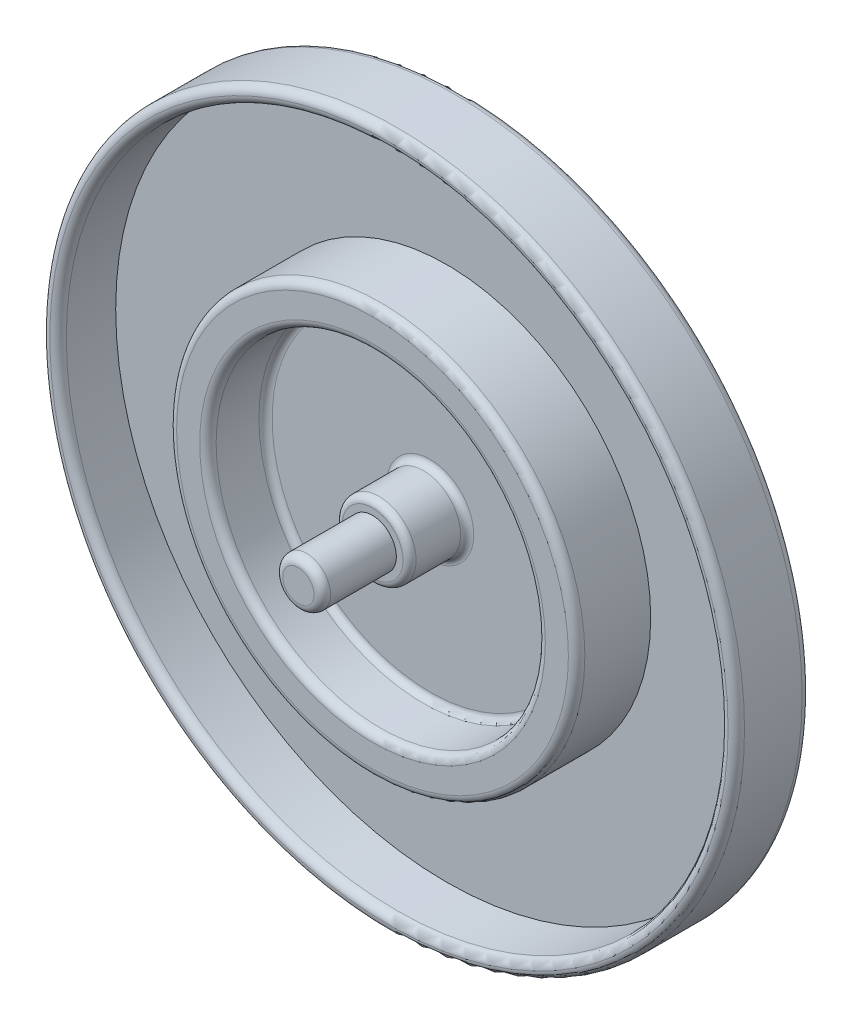
SolidWorks part; units mm, degrees
ref_plane "Front Plane" through (0, 0, 0) normal (0, 0, 1) x (1, 0, 0)
ref_plane "Top Plane" through (0, 0, 0) normal (0, 1, 0) x (1, 0, 0)
ref_plane "Right Plane" through (0, 0, 0) normal (1, 0, 0) x (0, 0, -1)
sketch "Sketch1" plane through (0, 0, 0) normal (0, 0, 1) x (1, 0, 0)
  circle A2 centre (0, 0) radius 12.4
  circle A3 centre (0, 0) radius 20.1
  circle A4 centre (0, 0) radius 10
  circle A5 centre (0, 0) radius 21.1
  dimension "D1" = 24.8
  dimension "D2" = 40.2
  dimension "D3" = 20
  dimension "D4" = 42.2
extrude "Boss-Extrude1" add sketch "Sketch1" along normal blind 4.5 contours A2 A4 | A5 A3 region at (-12.0493, 0, 0) region at (-20.5032, 0, 0)
sketch "Sketch6" plane through (0, 0, 4.5) normal (0, 0, 1) x (1, 0, 0)
  circle A0 centre (0, 0) radius 20.1 construction
  circle A1 centre (0, 0) radius 21.1
  circle A2 centre (0, 0) radius 21.1
  circle A3 centre (0, 0) radius 20.1
  dimension "D1" = 0
extrude "Cut-Extrude1" cut sketch "Sketch6" against normal blind 1
sketch "Sketch2" plane through (0, 0, 0) normal (0, 0, -1) x (-1, 0, 0)
  circle A0 centre (0, 0) radius 21.1 construction
  circle A1 centre (0, 0) radius 21.1
extrude "Boss-Extrude2" add sketch "Sketch2" along normal blind 1
sketch "Sketch3" plane through (0, 0, 0) normal (0, 0, 1) x (1, 0, 0)
  circle A0 centre (0, 0) radius 1.45
  dimension "D1" = 2.9
extrude "Boss-Extrude3" add sketch "Sketch3" along normal blind 9
fillet "Fillet1" radius 0.5 6 edges at (1.45, 0, 9) (10, 0, 4.5) (12.4, 0, 4.5) (-21.1, 0, -1) (20.1, 0, 3.5) (21.1, 0, 3.5)
sketch "Sketch4" plane through (0, 0, 0) normal (0, 0, 1) x (1, 0, 0)
  circle A0 centre (0, 0) radius 10 construction
  circle A1 centre (0, 0) radius 10
extrude "Boss-Extrude4" add sketch "Sketch4" along normal blind 1
sketch "Sketch5" plane through (0, 0, 1) normal (0, 0, 1) x (1, 0, 0)
  circle A0 centre (0, 0) radius 2.25
  circle A1 centre (0, 0) radius 1.45 construction
  dimension "D1" = 0.8
extrude "Boss-Extrude5" add sketch "Sketch5" along normal blind 3.5
fillet "Fillet2" radius 0.4 3 edges at (10, 0, 1) (2.25, 0, 4.5) (2.25, 0, 1)
